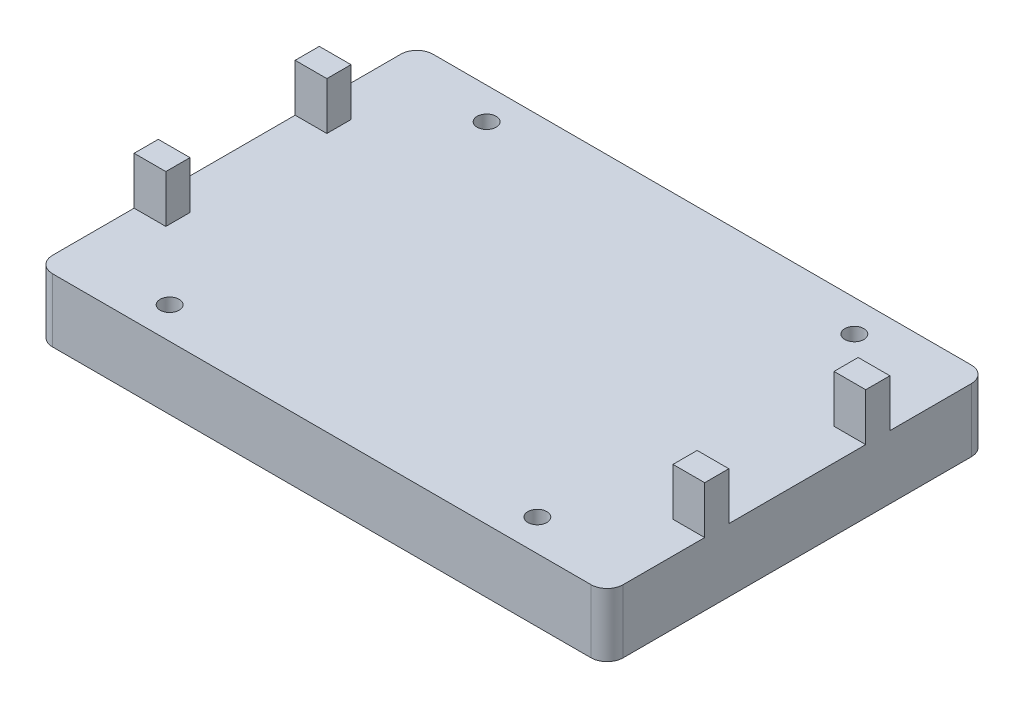
SolidWorks part; units mm, degrees
ref_plane "Front Plane" through (0, 0, 0) normal (0, 0, 1) x (1, 0, 0)
ref_plane "Top Plane" through (0, 0, 0) normal (0, 1, 0) x (1, 0, 0)
ref_plane "Right Plane" through (0, 0, 0) normal (1, 0, 0) x (0, 0, -1)
sketch "Sketch1" plane through (0, 0, 0) normal (0, 1, 0) x (1, 0, 0)
  line L1 (45, -30) -> (-45, -30)
  line L2 (45, -30) -> (45, 30)
  line L3 (45, 30) -> (-45, 30)
  line L4 (-45, -30) -> (-45, 30)
  line L5 (45, -30) -> (-45, 30) construction
  line L6 (45, 30) -> (-45, -30) construction
  point P0 (0, 0)
  dimension "D1" = 60
  dimension "D2" = 90
extrude "Boss-Extrude1" add sketch "Sketch1" along normal blind 10
sketch "Sketch2" plane through (0, 0, 0) normal (0, -1, 0) x (1, 0, 0)
  line L5 (45, -30) -> (-45, 30) construction
  line L6 (45, 30) -> (-45, -30) construction
  line L11 (-45, 30) -> (-35, 30)
  line L12 (-45, 30) -> (-45, 20)
  line L13 (-45, 20) -> (-35, 20)
  line L14 (-35, 30) -> (-35, 20)
  line L15 (-45, -30) -> (-35, -30)
  line L16 (-45, -30) -> (-45, -20)
  line L17 (-45, -20) -> (-35, -20)
  line L18 (-35, -30) -> (-35, -20)
  line L19 (35, -20) -> (45, -20)
  line L20 (35, -20) -> (35, -30)
  line L21 (35, -30) -> (45, -30)
  line L22 (45, -20) -> (45, -30)
  line L23 (35, 20) -> (45, 20)
  line L24 (35, 20) -> (35, 30)
  line L25 (35, 30) -> (45, 30)
  line L26 (45, 20) -> (45, 30)
  point P0 (0, 0)
sketch "Sketch4" plane through (-45, 0, 0) normal (-1, 0, 0) x (0, 0, 1)
  line L0 (0, 10) -> (0, 0)
  line L1 (-30, 10) -> (30, 10) construction
  line L2 (10.795, 10) -> (14.605, 10)
  line L3 (-14.605, 10) -> (-10.795, 10)
  line L4 (-14.605, 10) -> (14.605, 10) construction
  line L5 (14.605, 17.5) -> (14.605, 2.5)
  line L6 (14.605, 2.5) -> (10.795, 2.5)
  line L7 (10.795, 17.5) -> (10.795, 2.5)
  line L9 (-14.605, 17.5) -> (-14.605, 2.5)
  line L10 (-14.605, 2.5) -> (-10.795, 2.5)
  line L11 (-10.795, 17.5) -> (-10.795, 2.5)
  line L13 (14.605, 17.5) -> (10.795, 17.5)
  line L14 (-14.605, 17.5) -> (-10.795, 17.5)
  point P8 (0, 5)
  line M3 (30, 10) -> (-30, 10)
  dimension "D1" = 7.5
extrude "Boss-Extrude2" add sketch "Sketch4" against normal blind 5 contours L14 L9 L11 M3 | L5 L13 L7 M3 region at (-45, 13.75, 12.7) region at (-45, 13.75, -12.7)
mirror "Mirror1" about plane through (0, 0, 0) normal (1, 0, 0) of "Boss-Extrude2"
sketch "Sketch5" plane through (0, 0, 0) normal (0, -1, 0) x (1, 0, 0)
  line L6 (29, -25) -> (-29, 25) construction
  line L7 (29, 25) -> (-29, -25) construction
  circle A0 centre (-29, 25) radius 1.5
  circle A1 centre (-29, -25) radius 1.5
  circle A2 centre (29, 25) radius 1.5
  circle A3 centre (29, -25) radius 1.5
  point P2 (0, 0)
  dimension "D3" = 3
  dimension "D4" = 3
  dimension "D5" = 3
  dimension "D6" = 3
  dimension "D1" = 50
  dimension "D2" = 58
extrude "Cut-Extrude1" cut sketch "Sketch5" against normal up to surface (10 mm away) up to face at (0, 10, 0)
fillet "Fillet1" radius 2.54 4 edges at (-45, 5, 30) (45, 5, 30) (45, 5, -30) (-45, 5, -30)
